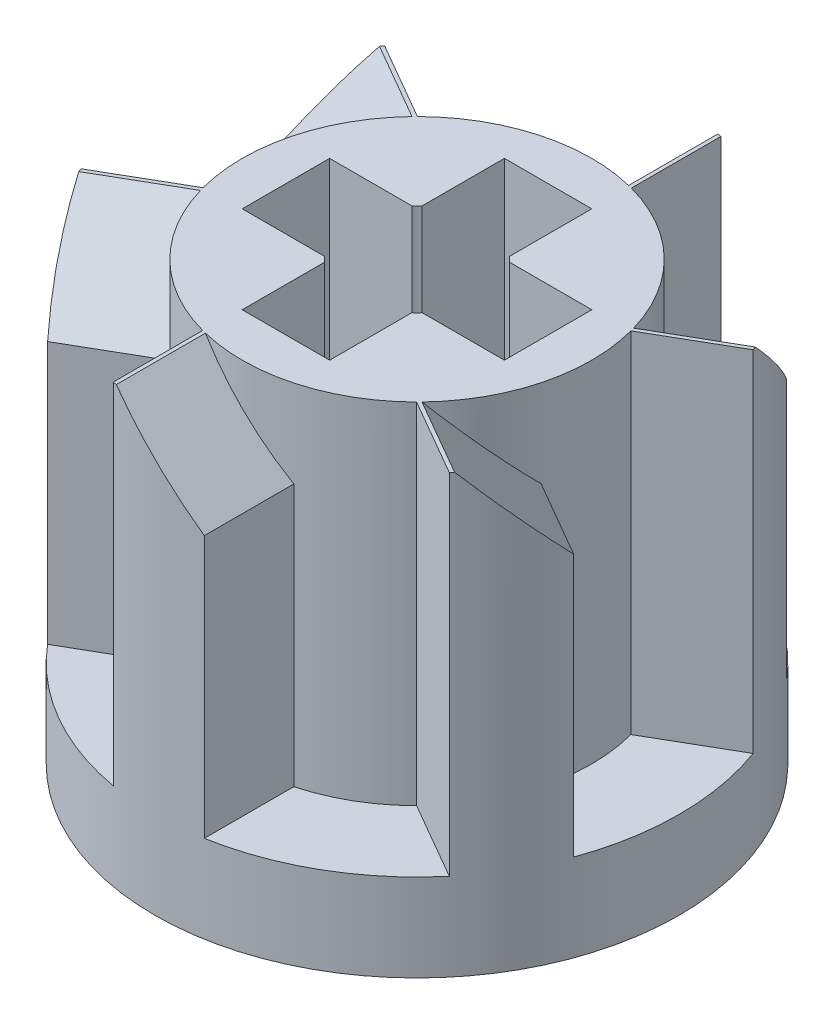
SolidWorks part; units mm, degrees
ref_plane "Front Plane" through (0, 0, 0) normal (0, 0, 1) x (1, 0, 0)
ref_plane "Top Plane" through (0, 0, 0) normal (0, 1, 0) x (1, 0, 0)
ref_plane "Right Plane" through (0, 0, 0) normal (1, 0, 0) x (0, 0, -1)
sketch "Sketch1" plane through (0, 0, 0) normal (0, 1, 0) x (1, 0, 0)
  circle A0 centre (0, 0) radius 6
  dimension "D1" = 12
extrude "Boss-Extrude1" add sketch "Sketch1" along normal blind 2
sketch "Sketch2" plane through (0, 2, 0) normal (0, 1, 0) x (1, 0, 0)
  circle A0 centre (0, 0) radius 4
  dimension "D1" = 8
extrude "Boss-Extrude2" add sketch "Sketch2" along normal blind 8
sketch "Sketch3" plane through (0, 10, 0) normal (0, 1, 0) x (1, 0, 0)
  line L5 (-3, 1) -> (3, 1)
  line L6 (-3, 1) -> (-3, -1)
  line L7 (-3, -1) -> (3, -1)
  line L8 (3, 1) -> (3, -1)
  line L9 (-3, 1) -> (3, -1) construction
  line L10 (-3, -1) -> (3, 1) construction
  point P0 (0, 0)
  dimension "D1" = 6
  dimension "D2" = 2
extrude "Cut-Extrude1" cut sketch "Sketch3" against normal through all
sketch "Sketch4" plane through (0, 10, 0) normal (0, 1, 0) x (1, 0, 0)
  line L1 (-1, 3) -> (1, 3)
  line L2 (-1, 3) -> (-1, -3)
  line L3 (-1, -3) -> (1, -3)
  line L4 (1, 3) -> (1, -3)
  line L5 (-1, 3) -> (1, -3) construction
  line L6 (-1, -3) -> (1, 3) construction
  point P0 (0, 0)
  dimension "D1" = 2
  dimension "D2" = 6
extrude "Cut-Extrude2" cut sketch "Sketch4" against normal blind 8
sketch "Sketch10" plane through (0, 10, 0) normal (0, 1, 0) x (1, 0, 0)
  circle A0 centre (0, 0) radius 1.5
  dimension "D1" = 3
extrude "Cut-Extrude3" cut sketch "Sketch10" against normal through all
sketch "Sketch11" plane through (0, 10, 0) normal (0, 1, 0) x (1, 0, 0)
  line L3 (-1.0419, 5.9088) -> (-1.0427, 3.8617)
  line L4 (1.0419, 5.9088) -> (1.0419, 3.8619)
  line L5 (-1.0427, 3.8617) -> (1.0419, 3.8619)
  line L6 (4.5963, 3.8567) -> (2.823, 2.8338)
  line L7 (5.6382, 2.0521) -> (3.8655, 1.0287)
  line L8 (2.823, 2.8338) -> (3.8655, 1.0287)
  line L9 (5.6382, -2.0521) -> (3.8657, -1.0279)
  line L10 (4.5963, -3.8567) -> (2.8236, -2.8333)
  line L11 (3.8657, -1.0279) -> (2.8236, -2.8333)
  line L12 (1.0419, -5.9088) -> (1.0427, -3.8617)
  line L13 (-1.0419, -5.9088) -> (-1.0419, -3.8619)
  line L14 (1.0427, -3.8617) -> (-1.0419, -3.8619)
  line L15 (-4.5963, -3.8567) -> (-2.823, -2.8338)
  line L16 (-5.6382, -2.0521) -> (-3.8655, -1.0287)
  line L17 (-2.823, -2.8338) -> (-3.8655, -1.0287)
  line L18 (-5.6382, 2.0521) -> (-3.8657, 1.0279)
  line L19 (-4.5963, 3.8567) -> (-2.8236, 2.8333)
  line L20 (-3.8657, 1.0279) -> (-2.8236, 2.8333)
  arc A0 (-1.0419, 5.9088) -> (1.0419, 5.9088) centre (0, 0) cw
  circle A2 centre (0, 0) radius 6 construction
  circle A3 centre (0, 0) radius 4 construction
  arc A4 (4.5963, 3.8567) -> (5.6382, 2.0521) centre (0, 0) cw
  arc A5 (5.6382, -2.0521) -> (4.5963, -3.8567) centre (0, 0) cw
  arc A6 (1.0419, -5.9088) -> (-1.0419, -5.9088) centre (0, 0) cw
  arc A7 (-4.5963, -3.8567) -> (-5.6382, -2.0521) centre (0, 0) cw
  arc A8 (-5.6382, 2.0521) -> (-4.5963, 3.8567) centre (0, 0) cw
  dimension "D3" = 6
extrude "Boss-Extrude3" add sketch "Sketch11" against normal up to surface (8 mm away) up to face at (0, 2, 4)
chamfer "Chamfer3" distance 2 angle 45 6 edges at (-4.7519, 10, -1.54) (-3.7096, 10, 3.3453) (1.0423, 10, 4.8853) (4.7519, 10, 1.54) (3.7096, 10, -3.3453) (-1.0423, 10, -4.8853)
